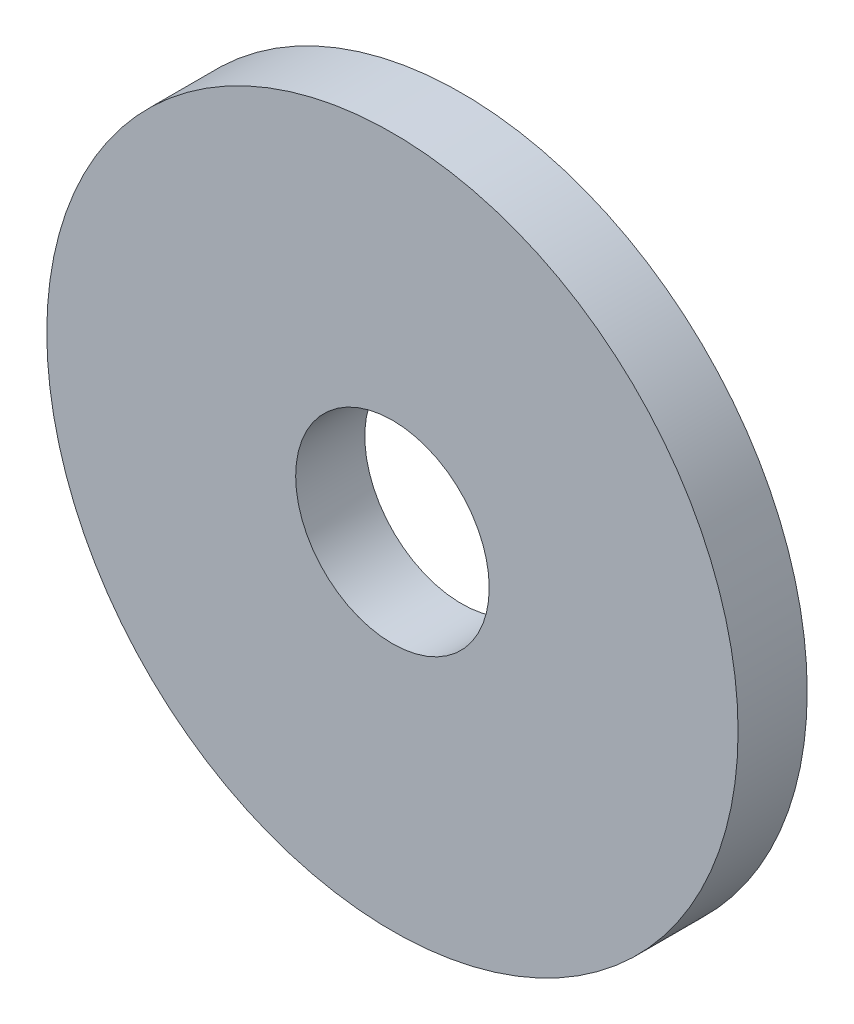
SolidWorks part; units mm, degrees
material "ABS"
ref_plane "Front Plane" through (0, 0, 0) normal (0, 0, 1) x (1, 0, 0)
ref_plane "Top Plane" through (0, 0, 0) normal (0, 1, 0) x (1, 0, 0)
ref_plane "Right Plane" through (0, 0, 0) normal (1, 0, 0) x (0, 0, -1)
sketch "Sketch1" plane through (0, 0, 0) normal (0, 0, 1) x (1, 0, 0)
  circle A0 centre (95.8641, 45.4656) radius 8.001
  circle A1 centre (95.8641, 45.4656) radius 19.05
  dimension "D1" = 16.002
  dimension "D2" = 38.1
extrude "Boss-Extrude1" add sketch "Sketch1" against normal blind 3.175
sketch "Sketch2" plane through (0, 0, 0) normal (0, 0, 1) x (1, 0, 0)
  circle A0 centre (95.8641, 45.4656) radius 19.05 construction
  circle A1 centre (95.8641, 45.4656) radius 19.05
extrude "Boss-Extrude2" add sketch "Sketch2" along normal blind 4.7625
hole_wizard "3/8 Clearance Hole1" positions "Sketch5" profile "Sketch3" hole size "3/8" standard "ANSI Inch" end condition through all
sketch "Sketch5" plane through (0, 0, 4.7625) normal (0, 0, 1) x (1, 0, 0)
  point P0 (95.8641, 45.4656)
sketch "Sketch3" plane through (95.8641, 45.4656, 4.7625) normal (1, 0, 0) x (0, -1, 0)
  line L0 (0, 0) -> (0, 7.9375)
  line L1 (0, 7.9375) -> (5.1587, 7.9375)
  line L2 (5.1587, 7.9375) -> (5.1587, 0)
  line L5 (5.1587, 0) -> (0, 0)
  line L11 (0, -6.35) -> (0, 107.95) construction
  dimension "Thru Hole Dia." = 10.3175
  dimension "Thru Hole Depth" = 7.9375
sketch "Sketch6" plane through (0, 0, 0) normal (0, 0, -1) x (-1, 0, 0)
  circle A0 centre (-95.8641, 45.4656) radius 8.001
  dimension "D1" = 16.002
extrude "Cut-Extrude1" cut sketch "Sketch6" against normal blind 2.54
sketch "Sketch7" plane through (0, 0, 4.7625) normal (0, 0, 1) x (1, 0, 0)
  circle A0 centre (95.8641, 45.4656) radius 19.05
  dimension "D1" = 38.1
extrude "Cut-Extrude2" cut sketch "Sketch7" against normal up to surface (2.2225 mm away) up to face at (87.8631, 45.4656, 2.54)
sketch "Sketch8" plane through (0, 0, -3.175) normal (0, 0, -1) x (-1, 0, 0)
  circle A0 centre (-95.8641, 45.4656) radius 28.575
  circle A1 centre (-95.8641, 45.4656) radius 19.05
  dimension "D1" = 57.15
  dimension "D2" = 38.1
extrude "Boss-Extrude3" add sketch "Sketch8" against normal up to surface (5.715 mm away) up to face at (76.8141, 45.4656, 2.54)
